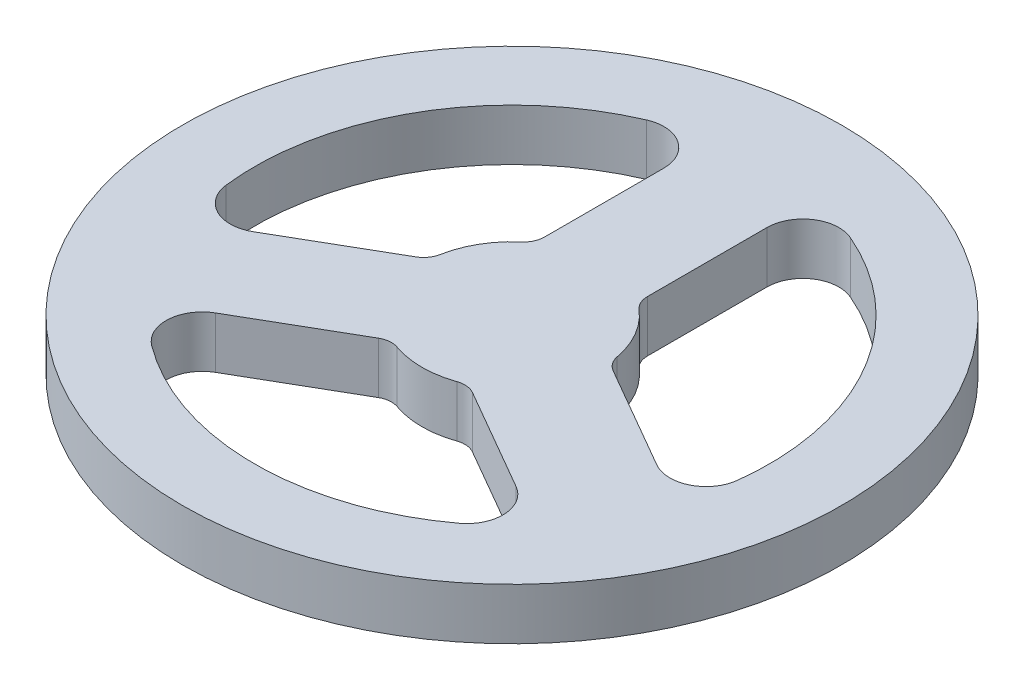
SolidWorks part; units mm, degrees
material "HYPALON"
ref_plane "Front Plane" through (0, 0, 0) normal (0, 0, 1) x (1, 0, 0)
ref_plane "Top Plane" through (0, 0, 0) normal (0, 1, 0) x (1, 0, 0)
ref_plane "Right Plane" through (0, 0, 0) normal (1, 0, 0) x (0, 0, -1)
sketch "Szkic1" plane through (0, 0, 0) normal (0, 1, 0) x (1, 0, 0)
  line L0 (0, 0) -> (-10, 0)
  line L1 (-10, 0) -> (0, 0)
  line L2 (0, 0) -> (10, 0)
  line L3 (-10, 0) -> (-10, 14.3614)
  line L4 (10, 0) -> (10, 14.3614)
  line L5 (7.4373, -15.841) -> (37.4264, -33.1552)
  line L6 (-10, 14.3614) -> (-10, 48.9898)
  line L7 (10, 14.3614) -> (10, 48.9898)
  line L8 (17.4373, 1.4796) -> (47.4264, -15.8346)
  line L9 (-17.4373, 1.4796) -> (-47.4264, -15.8346)
  line L10 (-7.4373, -15.841) -> (-37.4264, -33.1552)
  circle A0 centre (0, 0) radius 64
  circle A1 centre (0, 0) radius 50
  circle A2 centre (0, 0) radius 17.5
  point P22 (0, 0)
  dimension "D1" = 128
  dimension "D2" = 100
  dimension "D5" = 35
  dimension "D3" = 10
  dimension "D4" = 10
  dimension "D6" = 3
extrude "Dodanie-wyciągnięcie1" add sketch "Szkic1" along normal blind 10 contours A2 L9 A1 L10 | A2 L4 L2 L0 L3 | L4 A2 L3 L0 L2 | A2 L7 A1 L6 | A2 L5 A1 L8 | A0 A1 region at (0, 0, 4.3168) region at (0, 0, -8.273) region at (0, 0, -33.0681) region at (-28.6378, 0, 16.5341) region at (28.6378, 0, 16.5341) region at (-62.1898, 0, 0)
fillet "Zaokrąglenie1" radius 7 6 edges at (10, 5, -48.9898) (37.4264, 5, 33.1552) (-10, 5, -48.9898) (47.4264, 5, 15.8346) (-47.4264, 5, 15.8346) (-37.4264, 5, 33.1552)
fillet "Zaokrąglenie2" radius 4 6 edges at (17.4373, 5, -1.4796) (10, 5, -14.3614) (-7.4373, 5, 15.841) (7.4373, 5, 15.841) (-17.4373, 5, -1.4796) (-10, 5, -14.3614)
sketch "Szkic2" plane through (0, 0, 0) normal (0, 1, 0) x (1, 0, 0)
  circle A0 centre (0, 0) radius 35
  circle A1 centre (0, 0) radius 64
  dimension "D1" = 128
  dimension "D2" = 70
